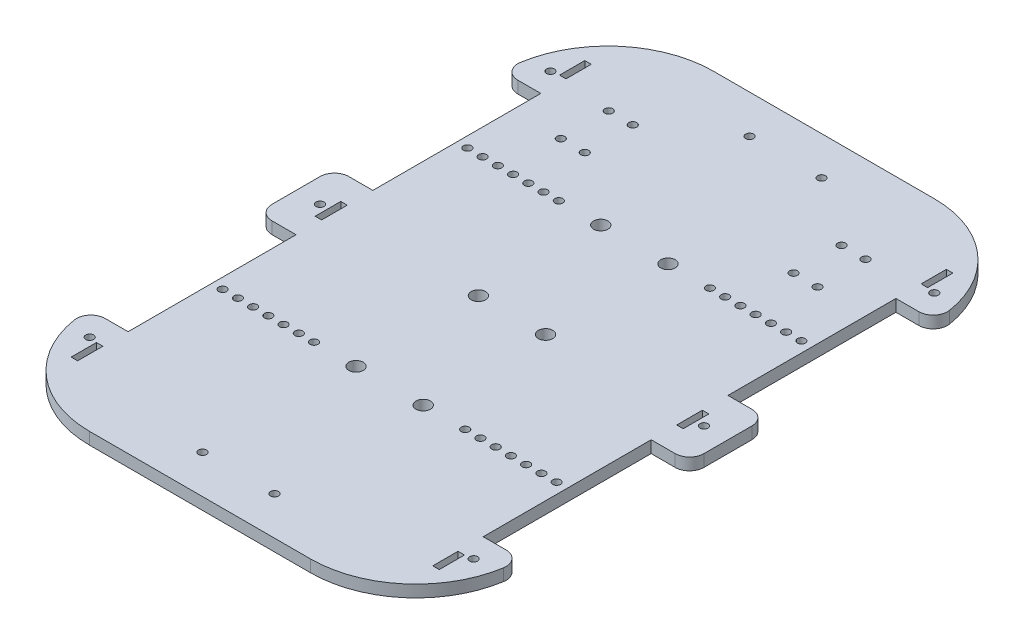
SolidWorks part; units mm, degrees
ref_plane "Ön Düzlem" through (0, 0, 0) normal (0, 0, 1) x (1, 0, 0)
ref_plane "Üst Düzlem" through (0, 0, 0) normal (0, 1, 0) x (1, 0, 0)
ref_plane "Sağ Düzlem" through (0, 0, 0) normal (1, 0, 0) x (0, 0, -1)
sketch "Sketch2" plane through (0, 0, 0) normal (0, 1, 0) x (1, 0, 0)
  line L0 (-74, -86) -> (-74, -51) construction
  line L1 (46, -130) -> (-46, -130)
  line L2 (90, -10) -> (90, 10)
  line L3 (46, 130) -> (-46, 130)
  line L4 (-90, -10) -> (-90, 10)
  line L5 (90, -130) -> (-90, 130) construction
  line L6 (90, 130) -> (-90, -130) construction
  line L7 (-83.5233, 86) -> (-74, 86)
  line L9 (-84, 16) -> (-74, 16)
  line L10 (-74, 86) -> (-74, 16)
  line L11 (-83.5233, -86) -> (-74, -86)
  line L13 (-84, -16) -> (-74, -16)
  line L14 (-74, -86) -> (-74, -16)
  line L15 (83.5233, 86) -> (74, 86)
  line L17 (84, 16) -> (74, 16)
  line L18 (74, 86) -> (74, 16)
  line L19 (83.5233, -86) -> (74, -86)
  line L21 (84, -16) -> (74, -16)
  line L22 (74, -86) -> (74, -16)
  line L23 (-74, 51) -> (74, 51) construction
  line L24 (-74, -51) -> (74, -51) construction
  line L26 (-74, 96.51) -> (-76.7, 96.51)
  line L27 (-76.7, 96.51) -> (-76.7, 107.02)
  line L28 (-74, 107.02) -> (-76.7, 107.02)
  line L29 (-74, 96.51) -> (-74, 107.02)
  line L30 (74, 96.51) -> (74, 107.02)
  line L31 (74, 107.02) -> (76.7, 107.02)
  line L32 (76.7, 96.51) -> (76.7, 107.02)
  line L33 (74, 96.51) -> (76.7, 96.51)
  line L34 (74, -107.02) -> (76.7, -107.02)
  line L35 (76.7, -96.51) -> (76.7, -107.02)
  line L36 (74, -96.51) -> (74, -107.02)
  line L37 (74, -96.51) -> (76.7, -96.51)
  line L38 (-74, -96.51) -> (-74, -107.02)
  line L39 (-74, -107.02) -> (-76.7, -107.02)
  line L40 (-76.7, -96.51) -> (-76.7, -107.02)
  line L41 (-74, -96.51) -> (-76.7, -96.51)
  line L42 (-74, 5.3333) -> (-74, -5.3333)
  line L43 (74, 5.3333) -> (74, -5.3333)
  line L44 (-74, 5.3333) -> (-76.7, 5.3333)
  line L45 (-76.7, 5.3333) -> (-76.7, -5.3333)
  line L46 (-76.7, -5.3333) -> (-74, -5.3333)
  line L47 (74, 5.3333) -> (76.7, 5.3333)
  line L48 (76.7, 5.3333) -> (76.7, -5.3333)
  line L49 (76.7, -5.3333) -> (74, -5.3333)
  arc A2 (-46, -130) -> (-89.4481, -92.9474) centre (-46, -86) cw
  arc A3 (-89.4481, 92.9474) -> (-46, 130) centre (-46, 86) cw
  arc A4 (89.4481, 92.9474) -> (46, 130) centre (46, 86) ccw
  arc A5 (89.4481, -92.9474) -> (46, -130) centre (46, -86) cw
  arc A6 (-84, 16) -> (-90, 10) centre (-84, 10) ccw
  arc A7 (-84, -16) -> (-90, -10) centre (-84, -10) cw
  arc A8 (90, 10) -> (84, 16) centre (84, 10) ccw
  arc A9 (90, -10) -> (84, -16) centre (84, -10) cw
  arc A10 (-89.4481, -92.9474) -> (-83.5233, -86) centre (-83.5233, -92) cw
  arc A11 (83.5233, -86) -> (89.4481, -92.9474) centre (83.5233, -92) cw
  arc A12 (-89.4481, 92.9474) -> (-83.5233, 86) centre (-83.5233, 92) ccw
  arc A13 (89.4481, 92.9474) -> (83.5233, 86) centre (83.5233, 92) cw
  point P0 (0, 0)
  point P34 (-90, -16)
  point P39 (90, -16)
  point P46 (-90, 86)
  point P49 (90, 86)
  dimension "D3" = 44
  dimension "D4" = 44
  dimension "D5" = 44
  dimension "D6" = 44
  dimension "D15" = 6
  dimension "D16" = 6
  dimension "D17" = 6
  dimension "D18" = 6
  dimension "D19" = 6
  dimension "D20" = 6
  dimension "D21" = 6
  dimension "D22" = 6
  dimension "D1" = 260
  dimension "D2" = 180
  dimension "D7" = 16
  dimension "D8" = 70
  dimension "D9" = 16
  dimension "D10" = 70
  dimension "D11" = 70
  dimension "D12" = 16
  dimension "D13" = 16
  dimension "D14" = 70
extrude "Boss-Extrude4" add sketch "Sketch2" along normal blind 5
sketch "Sketch5" plane through (0, 5, 0) normal (0, 1, 0) x (1, 0, 0)
  line L0 (-53.5, 73.83) -> (-43.5, 73.83) construction
  line L1 (-43.5, 73.83) -> (-43.5, 93.83) construction
  line L2 (-43.5, 93.83) -> (-43.5808, 93.8151) construction
  line L3 (-43.5808, 93.8151) -> (-53.5, 93.83) construction
  line L4 (-74, 86) -> (-74, 16) construction
  line L5 (53.5, 93.83) -> (43.5, 93.83) construction
  line L6 (43.5, 93.83) -> (43.5, 73.83) construction
  line L7 (43.5, 73.83) -> (53.5, 73.83) construction
  line L8 (74, 16) -> (74, 86) construction
  line L9 (46, 130) -> (-46, 130) construction
  circle A0 centre (-69.6, -51) radius 1.65
  circle A1 centre (-63.25, -51) radius 1.65
  circle A2 centre (-56.9, -51) radius 1.65
  circle A3 centre (-50.55, -51) radius 1.65
  circle A4 centre (-44.2, -51) radius 1.65
  circle A5 centre (-37.85, -51) radius 1.65
  circle A6 centre (-31.5, -51) radius 1.65
  circle A7 centre (31.5, -51) radius 1.65
  circle A8 centre (37.85, -51) radius 1.65
  circle A9 centre (44.2, -51) radius 1.65
  circle A10 centre (50.55, -51) radius 1.65
  circle A11 centre (56.9, -51) radius 1.65
  circle A12 centre (63.25, -51) radius 1.65
  circle A13 centre (69.6, -51) radius 1.65
  circle A14 centre (69.6, 51) radius 1.65
  circle A15 centre (63.25, 51) radius 1.65
  circle A16 centre (56.9, 51) radius 1.65
  circle A17 centre (50.55, 51) radius 1.65
  circle A18 centre (44.2, 51) radius 1.65
  circle A19 centre (37.85, 51) radius 1.65
  circle A20 centre (31.5, 51) radius 1.65
  circle A21 centre (-31.5, 51) radius 1.65
  circle A22 centre (-37.85, 51) radius 1.65
  circle A23 centre (-44.2, 51) radius 1.65
  circle A24 centre (-50.55, 51) radius 1.65
  circle A25 centre (-56.9, 51) radius 1.65
  circle A26 centre (-63.25, 51) radius 1.65
  circle A27 centre (-69.6, 51) radius 1.65
  circle A29 centre (-14, -51) radius 3
  circle A30 centre (14, -51) radius 3
  circle A31 centre (14, 51) radius 3
  circle A32 centre (-14, 51) radius 3
  circle A33 centre (-14, 0) radius 3
  circle A34 centre (14, 0) radius 3
  circle A35 centre (-80, 96) radius 1.65
  circle A36 centre (-80, 0) radius 1.65
  circle A37 centre (80, 0) radius 1.65
  circle A38 centre (-80, -96) radius 1.65
  circle A39 centre (80, -96) radius 1.65
  circle A40 centre (80, 96) radius 1.65
  circle A41 centre (-15, -114) radius 1.65
  circle A42 centre (15, -114) radius 1.65
  circle A43 centre (15, 114) radius 1.65
  circle A44 centre (-15, 114) radius 1.65
  circle A45 centre (-53.5, 93.83) radius 1.65
  circle A46 centre (-53.5, 73.83) radius 1.65
  circle A47 centre (-43.5, 73.83) radius 1.65
  circle A48 centre (-43.5, 93.83) radius 1.65
  circle A49 centre (43.5, 73.83) radius 1.65
  circle A50 centre (53.5, 73.83) radius 1.65
  circle A51 centre (43.5, 93.83) radius 1.65
  circle A52 centre (53.5, 93.83) radius 1.65
  dimension "D1" = 20.5
  dimension "D2" = 20.5
  dimension "D3" = 36.17
  dimension "D4" = 56.17
  dimension "D5" = 56.17
extrude "Cut-Extrude1" cut sketch "Sketch5" against normal through all
